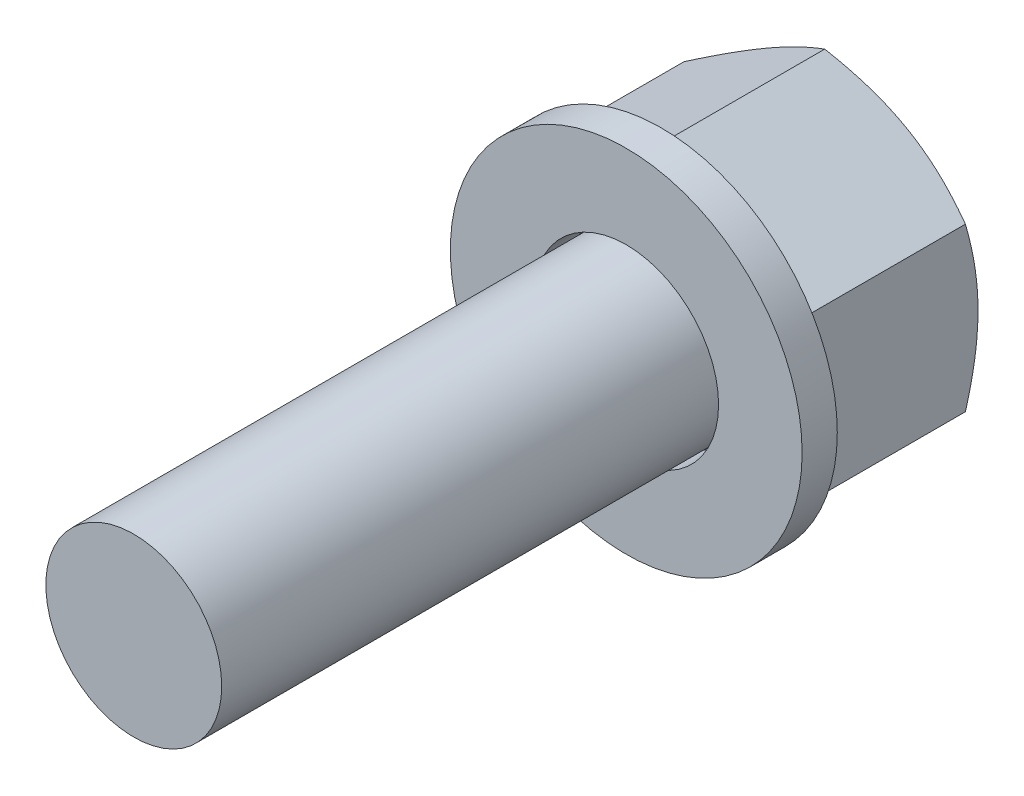
SolidWorks part; units mm, degrees
other "Vite"
other "Rosetta"
ref_plane "Piano frontale" through (0, 0, 0) normal (0, 0, 1) x (1, 0, 0)
ref_plane "Piano superiore" through (0, 0, 0) normal (0, 1, 0) x (1, 0, 0)
ref_plane "Piano destro" through (0, 0, 0) normal (1, 0, 0) x (0, 0, -1)
sketch "Sketch1" plane through (0, 0, 0) normal (0, 0, 1) x (1, 0, 0)
  line L1 (-3.1632, 12.1549) -> (-11.1632, 16.7737)
  line L2 (-11.1632, 16.7737) -> (-19.1632, 12.1549)
  line L3 (-19.1632, 12.1549) -> (-19.1632, 2.9173)
  line L4 (-19.1632, 2.9173) -> (-11.1632, -1.7015)
  line L5 (-11.1632, -1.7015) -> (-3.1632, 2.9173)
  line L6 (-3.1632, 2.9173) -> (-3.1632, 12.1549)
  circle A0 centre (-11.1632, 7.5361) radius 8 construction
  circle A1 centre (-11.1632, 7.5361) radius 5
  point P1 (0, 0)
  point P10 (0, 0)
  dimension "D1" = 10
  dimension "D2" = 16
extrude "Boss-Extrude1" add sketch "Sketch1" along normal blind 10 contours A1 | L5 L6 L1 L2 L3 L4 A1 region at (-3.4076, 7.5361, 0) region at (-11.1632, 7.5361, 0)
extrude "Boss-Extrude2" add sketch "Sketch1<3>" along normal blind 30 from surface contours A1 region at (-11.1632, 7.5361, 0) starting at face at (-11.1632, 7.5361, 10)
sketch "Sketch1<3>" plane through (0, 0, 0) normal (0, 0, 1) x (1, 0, 0) same geometry as "Sketch1"
sketch "Sketch3" plane through (0, 0, 0) normal (0, 0, 1) x (1, 0, 0)
  circle A0 centre (-11.1632, 7.5361) radius 10
  circle A1 centre (-11.1632, 7.5361) radius 5 construction
  circle A2 centre (-11.1632, 7.5361) radius 5.25
  dimension "D1" = 20
  dimension "D2" = 10.5
extrude "Boss-Extrude3" add sketch "Sketch3" along normal blind 2 from surface separate body starting at face at (-6.1632, 7.5361, 10)
ref_plane "Plane1" through (0, 7.5361, 0) normal (0, -1, 0) x (-1, 0, 0)
ref_plane "Plane2" through (-11.1632, 0, 0) normal (-1, 0, 0) x (0, 0, 1)
ref_axis "Axis1" through (-11.1632, 7.5361, 10.5) along (0, 0, -1)
sketch "Sketch6" plane through (0, 7.5361, 0) normal (0, -1, 0) x (-1, 0, 0)
  line L0 (16.0389, 4.8038) -> (16.0389, 1.8038)
  line L1 (16.0389, 1.8038) -> (28.1632, -5.1962)
  line L5 (30.0389, -5.1962) -> (30.0389, 4.8038)
  line L6 (30.0389, 4.8038) -> (16.0389, 4.8038)
  line L7 (16.0389, 1.8038) -> (24.4617, 1.8038) construction
  line L8 (28.1632, -5.1962) -> (30.0389, -5.1962)
  point P7 (19.1632, 0)
  point P10 (19.1632, -10)
  dimension "D1" = 10
  dimension "D2" = 30
  dimension "D3" = 3
  dimension "D4" = 14
  dimension "D5" = 9
revolve "Cut-Revolve2" cut sketch "Sketch6" angle 360 about axis through (-11.1632, 7.5361, 10.5) along (0, 0, -1)
